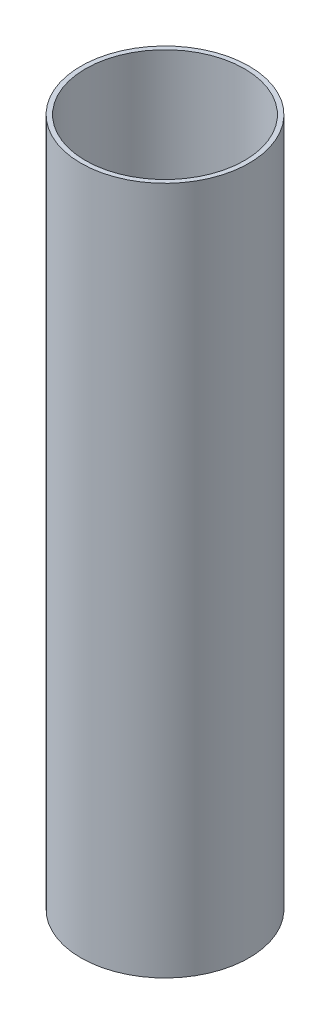
SolidWorks part; units mm, degrees
ref_plane "Front Plane" through (0, 0, 0) normal (0, 0, 1) x (1, 0, 0)
ref_plane "Top Plane" through (0, 0, 0) normal (0, 1, 0) x (1, 0, 0)
ref_plane "Right Plane" through (0, 0, 0) normal (1, 0, 0) x (0, 0, -1)
sketch "Sketch1" plane through (0, 0, 0) normal (0, 1, 0) x (1, 0, 0)
  circle A0 centre (0, 0) radius 52
  circle A1 centre (0, 0) radius 55
  dimension "D1" = 104
  dimension "D2" = 3
extrude "Boss-Extrude1" add sketch "Sketch1" along normal blind 450
